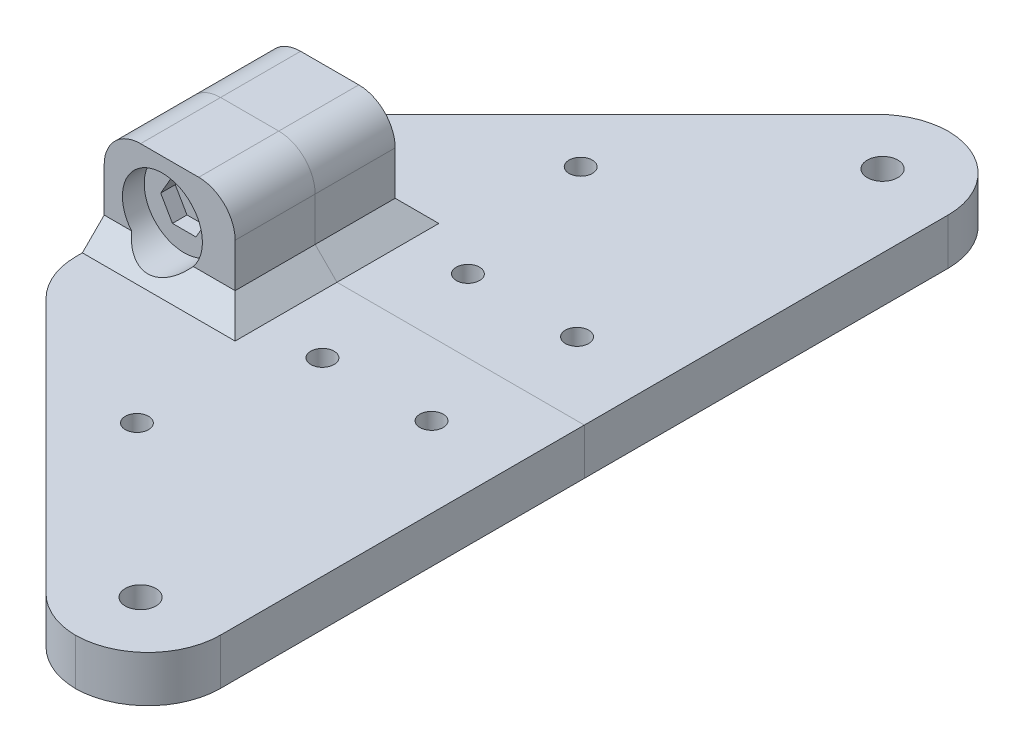
SolidWorks part; units mm, degrees
ref_plane "Front Plane" through (0, 0, 0) normal (0, 0, 1) x (1, 0, 0)
ref_plane "Top Plane" through (0, 0, 0) normal (0, 1, 0) x (1, 0, 0)
ref_plane "Right Plane" through (0, 0, 0) normal (1, 0, 0) x (0, 0, -1)
sketch "Sketch1" plane through (251.8861, -2636.0305, -0.2779) normal (0, 1, 0) x (1, 0, 0)
  line L0 (-265.8861, -0.2779) -> (-251.8861, -0.2779)
  line L1 (-251.8861, -0.2779) -> (-251.8861, 59.7221)
  line L2 (-251.8861, 59.7221) -> (-306.8861, 59.7221)
  line L3 (-306.8861, 59.7221) -> (-306.8861, 40.7221)
  line L4 (-306.8861, 40.7221) -> (-265.8861, -0.2779)
  line L5 (-262.8861, 49.7221) -> (-277.8861, 49.7221) construction
  circle A0 centre (-261.8861, 8.7221) radius 2.1
  circle A1 centre (-282.8861, 29.2221) radius 1.6
  circle A2 centre (-262.8861, 49.7221) radius 1.6
  circle A3 centre (-277.8861, 49.7221) radius 1.6
  dimension "D5" = 4.2
  dimension "D6" = 3.2
  dimension "D12" = 3.2
  dimension "D13" = 3.2
  dimension "D2" = 55
  dimension "D3" = 41
  dimension "D4" = 60
  dimension "D7" = 10
  dimension "D8" = 31
  dimension "D9" = 9
  dimension "D10" = 29.5
  dimension "D11" = 45
  dimension "D14" = 15
  dimension "D15" = 10
  dimension "D16" = 11
extrude "Boss-Extrude1" add sketch "Sketch1" along normal blind 6.35
ref_plane "Plane1" through (-55, -2629.6805, -60) normal (0, -1, 0) x (-1, 0, 0)
sketch "Sketch2" plane through (-55, -2629.6805, -60) normal (0, -1, 0) x (1, 0, 0)
  line L1 (0, 0) -> (18, 0)
  line L2 (0, 0) -> (0, 11)
  line L3 (0, 11) -> (18, 11)
  line L4 (18, 0) -> (18, 11)
  dimension "D1" = 11
  dimension "D2" = 18
extrude "Boss-Extrude2" add sketch "Sketch2" against normal blind 14
sketch "Sketch3" plane through (0, 0, -49) normal (0, 0, 1) x (1, 0, 0)
  line L0 (-37, -2629.6805) -> (-55, -2629.6805) construction
  line L3 (-55, -2615.6805) -> (-55, -2629.6805) construction
  circle A0 centre (-47, -2623.1805) radius 5.5
  dimension "D1" = 11
  dimension "D2" = 6.5
  dimension "D3" = 8
extrude "Cut-Extrude1" cut sketch "Sketch3" against normal blind 3
chamfer "Chamfer1" distance 3 angle 45 2 edges
fillet "Fillet2" radius 10 3 edges at (-14, -2632.8555, 0) (-55, -2632.8555, -41) (0, -2632.8555, 0)
fillet "Fillet3" radius 5 2 edges at (-37, -2615.6805, -54.5) (-55, -2615.6805, -54.5)
sketch "Sketch4" plane through (0, 0, -52) normal (0, 0, 1) x (1, 0, 0)
  line L1 (-45.3834, -2625.9805) -> (-43.7668, -2623.1805)
  line L2 (-43.7668, -2623.1805) -> (-45.3834, -2620.3805)
  line L3 (-45.3834, -2620.3805) -> (-48.6166, -2620.3805)
  line L4 (-48.6166, -2620.3805) -> (-50.2332, -2623.1805)
  line L5 (-50.2332, -2623.1805) -> (-48.6166, -2625.9805)
  line L6 (-48.6166, -2625.9805) -> (-45.3834, -2625.9805)
  circle A0 centre (-47, -2623.1805) radius 2.8 construction
  dimension "D1" = 5.6
extrude "Cut-Extrude2" cut sketch "Sketch4" against normal blind 2
sketch "Sketch5" plane through (0, 0, -54) normal (0, 0, 1) x (1, 0, 0)
  circle A0 centre (-47, -2623.1805) radius 1.6
  dimension "D1" = 3.2
extrude "Cut-Extrude3" cut sketch "Sketch5" against normal through all
sketch "Sketch6" plane through (0, 0, -60) normal (0, 0, -1) x (-1, 0, 0)
  circle A0 centre (47, -2623.1805) radius 2.95
  dimension "D1" = 5.9
extrude "Cut-Extrude4" cut sketch "Sketch6" against normal blind 3
mirror "Mirror2" about plane through (0, -2629.6805, -60) normal (0, 0, 1) of bodies 106
